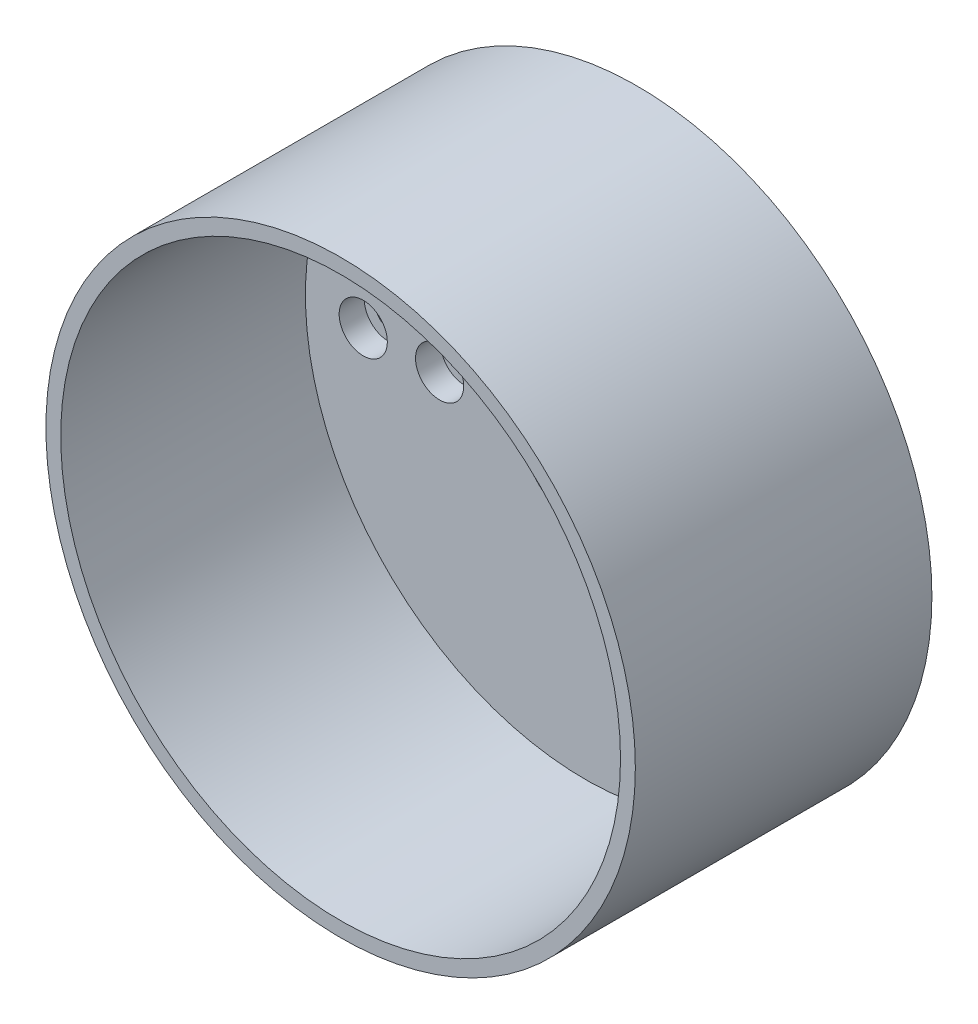
SolidWorks part; units mm, degrees
ref_plane "Front Plane" through (0, 0, 0) normal (0, 0, 1) x (1, 0, 0)
ref_plane "Top Plane" through (0, 0, 0) normal (0, 1, 0) x (1, 0, 0)
ref_plane "Right Plane" through (0, 0, 0) normal (1, 0, 0) x (0, 0, -1)
sketch "Sketch1" plane through (0, 0, 0) normal (0, 0, 1) x (1, 0, 0)
  circle A0 centre (0, 0) radius 37.75
  circle A1 centre (0, 0) radius 9
  circle A2 centre (0, 0) radius 39.75
  dimension "D1" = 75.5
  dimension "D2" = 18
  dimension "D3" = 2
extrude "Boss-Extrude1" add sketch "Sketch1" along normal blind 7 contours A1 | A0
sketch "Sketch2" plane through (0, 0, 7) normal (0, 0, 1) x (1, 0, 0)
  line L0 (0, 0) -> (-37.75, 0) construction
  circle A0 centre (0, 0) radius 37.75 construction
  circle A1 centre (-29.95, 0) radius 1.8
  circle A2 centre (-19.65, 0) radius 1.8
  circle A3 centre (-19.65, 0) radius 3.7 construction
  point P10 (-28.15, 0)
  point P11 (-21.45, 0)
  point P12 (-31.75, 0)
  point P14 (0, 0)
  dimension "D1" = 3.6
  dimension "D2" = 6.7
  dimension "D3" = 6
extrude "Boss-Extrude2" add sketch "Sketch1<5>" along normal blind 40 contours A2 A0 region at (-38.6257, 0, 0)
sketch "Sketch1<5>" plane through (0, 0, 0) normal (0, 0, 1) x (1, 0, 0) same geometry as "Sketch1"
ref_plane "Plane1" through (0, 0, -5) normal (0, 0, -1) x (-1, 0, 0)
sketch "Sketch5" plane through (0, 0, -5) normal (0, 0, -1) x (-1, 0, 0)
  line L0 (0, 0) -> (38.3956, 10.2881)
  line L1 (0, 0) -> (38.3956, -10.2881)
  line L2 (0, 0) -> (39.75, 0) construction
  circle A0 centre (0, 0) radius 9
  circle A1 centre (0, 0) radius 39.75
  dimension "D1" = 15
  dimension "D2" = 15
extrude "Boss-Extrude3" [suppressed] add sketch "Sketch5" against normal blind 6 contours A0 L2 A1 L0 | L2 A0 L1 A1
draft "Draft1" [suppressed] type of draft neutral plane draft angle 15 faces to draft 2 parameters "D1"=15
hole_wizard "CBORE for M3 Socket Head Cap Screw1" positions "3DSketch2" profile "Sketch4" counterbore size "M3" standard "DIN" end condition through all
sketch3d "3DSketch2"
  point P0 (-29.95, 0, 7)
  point P3 (-19.65, 0, 7)
sketch "Sketch4" plane through (-29.95, 0, 7) normal (1, 0, 0) x (0, -1, 0)
  line L0 (0, 0) -> (0, 7)
  line L1 (0, 7) -> (1.7, 7)
  line L3 (1.7, 7) -> (1.7, 3.4)
  line L4 (1.7, 3.4) -> (3.25, 3.4)
  line L5 (3.25, 3.4) -> (3.25, 0)
  line L7 (3.25, 0) -> (0, 0)
  line L11 (0, -6.35) -> (0, 107.95) construction
  dimension "Thru Hole Dia." = 3.4
  dimension "Thru Hole Depth" = 7
  dimension "C'Bore Dia." = 6.5
  dimension "C'Bore Depth" = 3.4
